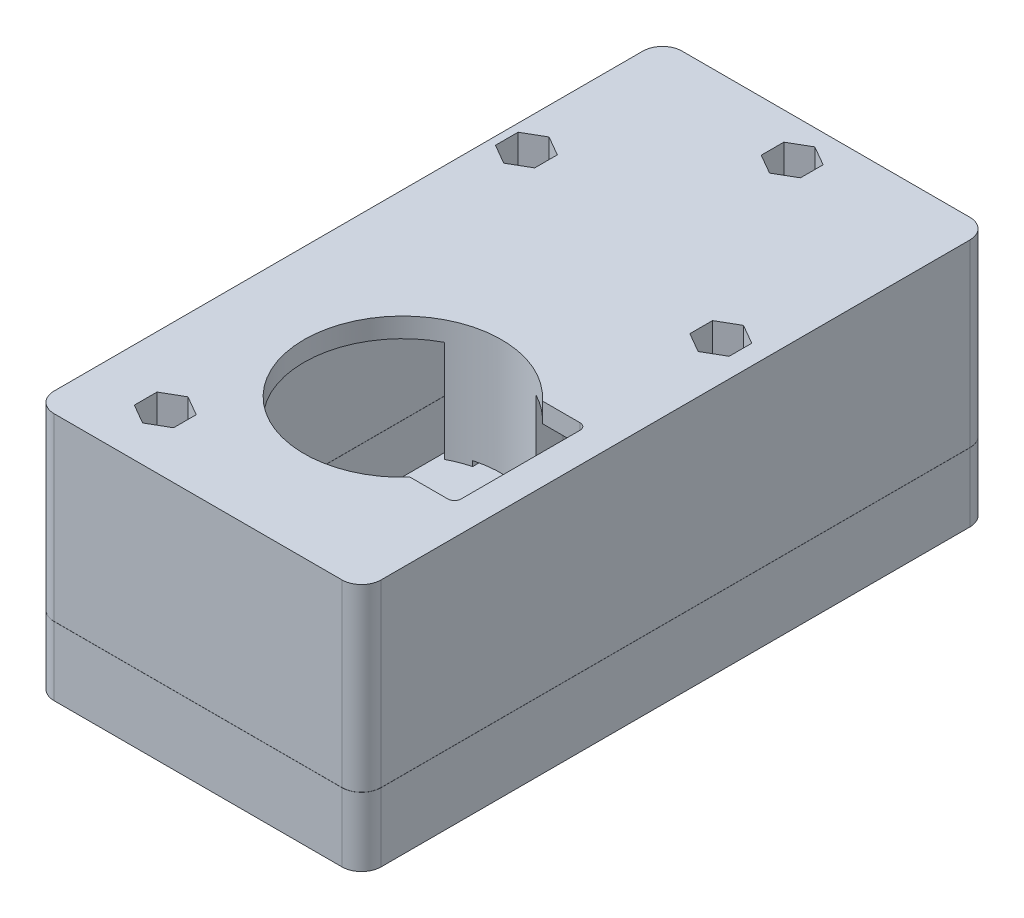
SolidWorks part; units mm, degrees
ref_plane "前视基准面" through (0, 0, 0) normal (0, 0, 1) x (1, 0, 0)
ref_plane "上视基准面" through (0, 0, 0) normal (0, 1, 0) x (1, 0, 0)
ref_plane "右视基准面" through (0, 0, 0) normal (1, 0, 0) x (0, 0, -1)
sketch "草图1" plane through (0, 0, 0) normal (0, 0, 1) x (1, 0, 0)
  line L1 (50, 38) -> (0, 38)
  line L2 (50, 38) -> (50, 0)
  line L3 (50, 0) -> (0, 0)
  line L4 (0, 38) -> (0, 0)
  dimension "D1" = 50
  dimension "D2" = 38
extrude "凸台-拉伸1" add sketch "草图1" against normal blind 3
sketch "草图2" plane through (0, 0, 0) normal (0, 0, 1) x (1, 0, 0)
  line L8 (50, 0) -> (50, 38)
  line L9 (50, 38) -> (0, 38)
  line L10 (0, 38) -> (0, 0)
  line L11 (0, 0) -> (50, 0)
  line L12 (50, 0) -> (50, 38)
  line L13 (50, 38) -> (0, 38)
  line L14 (0, 38) -> (0, 0)
  line L15 (0, 0) -> (50, 0)
  line L20 (47, 3) -> (47, 35)
  line L21 (47, 35) -> (3, 35)
  line L22 (3, 35) -> (3, 3)
  line L23 (3, 3) -> (47, 3)
  line L24 (47, 3) -> (47, 35)
  line L25 (47, 35) -> (3, 35)
  line L26 (3, 35) -> (3, 3)
  line L27 (3, 3) -> (47, 3)
  dimension "D1" = 0
  dimension "D2" = 3
extrude "凸台-拉伸2" add sketch "草图2" along normal blind 90
sketch "草图4" plane through (0, 0, -3) normal (0, 0, -1) x (-1, 0, 0)
  line L0 (-50, 38) -> (0, 38) construction
  line L1 (0, 38) -> (0, 0) construction
  circle A0 centre (-12.5, 10.5) radius 7.3
  dimension "D1" = 14.6
  dimension "D3" = 12.5
  dimension "D2" = 27.5
extrude "切除-拉伸1" cut sketch "草图4" against normal blind 45.2
sketch "草图5" plane through (0, 0, 0) normal (0, 0, 1) x (1, 0, 0)
  circle A0 centre (12.5, 10.5) radius 7.3
  circle A1 centre (12.5, 10.5) radius 7.3 construction
  circle A2 centre (12.5, 10.5) radius 10.3
  dimension "D1" = 3
extrude "凸台-拉伸3" add sketch "草图5" along normal blind 16
sketch "草图6" plane through (0, 0, -3) normal (0, 0, -1) x (-1, 0, 0)
  circle A0 centre (-12.5, 10.5) radius 5.8
  circle A3 centre (-12.5, 10.5) radius 7.3 construction
  circle A4 centre (-12.5, 10.5) radius 8.3
  circle A5 centre (-12.5, 10.5) radius 8.3
  dimension "D1" = 1
  dimension "D2" = 1.5
extrude "凸台-拉伸5" add sketch "草图6" against normal blind 1
sketch "草图7" plane through (0, 0, 16) normal (0, 0, 1) x (1, 0, 0)
  line L2 (5.4403, 3) -> (19.5597, 3)
  line L4 (5.4403, 3) -> (19.5597, 3)
  line L5 (3, 14.4799) -> (3, 6.5201)
  line L8 (3, 14.4799) -> (3, 6.5201)
  arc A1 (3, 6.5201) -> (5.4403, 3) centre (12.5, 10.5) ccw
  arc A2 (3, 6.5201) -> (5.4403, 3) centre (12.5, 10.5) ccw
  circle A3 centre (12.5, 10.5) radius 4.3
  arc A10 (19.5597, 3) -> (3, 14.4799) centre (12.5, 10.5) ccw
  arc A11 (19.5597, 3) -> (3, 14.4799) centre (12.5, 10.5) ccw
  dimension "D2" = 8.6
  dimension "D1" = 0
extrude "凸台-拉伸6" add sketch "草图7" along normal blind 2
sketch "草图8" plane through (0, 0, 18) normal (0, 0, 1) x (1, 0, 0)
  circle A1 centre (12.5, 10.5) radius 6.3
  circle A2 centre (12.5, 10.5) radius 4.3
  circle A3 centre (12.5, 10.5) radius 4.3
  dimension "D1" = 0
  dimension "D2" = 2
extrude "凸台-拉伸7" add sketch "草图8" along normal blind 10
sketch "草图9" plane through (0, 0, 28) normal (0, 0, 1) x (1, 0, 0)
  line L0 (8.2, 10.5) -> (16.8, 10.5) construction
  line L2 (16.1644, 8.25) -> (18.8, 8.25)
  line L3 (16.1644, 8.25) -> (16.1644, 12.75)
  line L4 (16.1644, 12.75) -> (18.8, 12.75)
  line L5 (18.8, 8.25) -> (18.8, 12.75)
  circle A0 centre (12.5, 10.5) radius 4.3 construction
  circle A1 centre (12.5, 10.5) radius 6.3 construction
  dimension "D1" = 4.5
extrude "切除-拉伸2" cut sketch "草图9" against normal blind 4
sketch "草图10" plane through (0, 3, 0) normal (0, 1, 0) x (1, 0, 0)
  line L0 (19.33, -36.76) -> (19.33, -34.76)
  line L1 (19.33, -34.76) -> (22.03, -34.76)
  line L2 (22.03, -34.76) -> (22.03, -36.76)
  line L3 (22.03, -36.76) -> (19.33, -36.76)
  line L8 (23.23, -37.46) -> (23.23, -28) construction
  line L9 (23.43, -37.46) -> (23.03, -37.46) construction
  line L10 (16.8, -28) -> (29.66, -28) construction
  line L11 (27.13, -34.76) -> (24.43, -34.76)
  line L12 (24.43, -34.76) -> (24.43, -36.76)
  line L13 (24.43, -36.76) -> (27.13, -36.76)
  line L14 (27.13, -36.76) -> (27.13, -34.76)
  line L15 (18.53, -37.26) -> (18.53, -34.14) construction
  line L16 (22.83, -37.26) -> (22.83, -34.14) construction
  line L17 (20.92, -34.36) -> (18.92, -34.36) construction
  circle A0 centre (19.92, -32.88) radius 0.7
  circle A1 centre (26.54, -32.88) radius 0.7
  circle A2 centre (19.92, -32.88) radius 0.98 construction
  point P14 (18.53, -35.7)
  dimension "D1" = 1.4
  dimension "D2" = 0.28
  dimension "D3" = 0.8
  dimension "D4" = 0.8
  dimension "D5" = 0.4
  dimension "D6" = 2
extrude "凸台-拉伸8" add sketch "草图10" along normal blind 32
sketch "草图11" plane through (0, 3, 0) normal (0, 1, 0) x (1, 0, 0)
  line L0 (16.8, -34.14) -> (16.8, -28) construction
  line L1 (16.2, -36.76) -> (30.26, -36.76)
  line L2 (16.2, -36.76) -> (16.2, -27.4)
  line L3 (16.2, -27.4) -> (30.26, -27.4)
  line L4 (30.26, -36.76) -> (30.26, -27.4)
  line L5 (29.66, -28) -> (29.66, -34.14) construction
  line L6 (19.33, -36.76) -> (22.03, -36.76) construction
  line L7 (16.8, -28) -> (29.66, -28) construction
  dimension "D1" = 0.6
  dimension "D2" = 0.6
  dimension "D3" = 0.6
extrude "凸台-拉伸9" add sketch "草图11" along normal blind 4.4
sketch "草图12" plane through (0, 35, 0) normal (0, -1, 0) x (1, 0, 0)
  line L1 (16.2, 27.4) -> (30.26, 27.4)
  line L2 (16.2, 27.4) -> (16.2, 36.76)
  line L3 (16.2, 36.76) -> (30.26, 36.76)
  line L4 (30.26, 27.4) -> (30.26, 36.76)
extrude "凸台-拉伸10" add sketch "草图12" along normal blind 21.2
sketch "草图13" plane through (0, 38, 0) normal (0, 1, 0) x (1, 0, 0)
  line L0 (12.3, -64.096) -> (42.5, -64.096) construction
  line L1 (40.04, -72.896) -> (39.0237, -72.896) construction
  line L2 (38.625, -74.196) -> (44.4, -74.196)
  line L3 (45.4, -73.196) -> (45.4, -54.996)
  line L4 (44.4, -57.796) -> (44.4, -70.396) construction
  line L5 (38.625, -53.996) -> (44.4, -53.996)
  circle A0 centre (27.4, -64.096) radius 15.1 construction
  circle A1 centre (27.4, -64.096) radius 14.1 construction
  arc A2 (38.625, -74.196) -> (38.625, -53.996) centre (27.4, -64.096) cw
  arc A3 (44.4, -53.996) -> (45.4, -54.996) centre (44.4, -54.996) cw
  arc A4 (44.4, -74.196) -> (45.4, -73.196) centre (44.4, -73.196) ccw
  point P16 (45.4, -64.096)
  point P18 (45.4, -53.996)
  point P21 (45.4, -74.196)
  dimension "D1" = 1
  dimension "D2" = 1.3
  dimension "D4" = 1
  dimension "D3" = 1
extrude "切除-拉伸3" cut sketch "草图13" against normal blind 3
sketch "草图14" plane through (0, 35, 0) normal (0, -1, 0) x (1, 0, 0)
  line L0 (14.3, 64.096) -> (40.5, 64.096) construction
  line L1 (23.9, 46.596) -> (23.9, 50.4373) construction
  line L2 (30.9, 46.596) -> (30.9, 50.4373) construction
  line L3 (23.9, 46.596) -> (23.9, 49.4072)
  line L4 (30.9, 46.596) -> (30.9, 49.4072)
  line L5 (30.9, 81.596) -> (30.9, 78.7847)
  line L6 (23.9, 81.596) -> (23.9, 78.7847)
  circle A0 centre (27.4, 46.596) radius 1.65
  circle A1 centre (27.4, 64.096) radius 13.1 construction
  arc A2 (23.9, 49.4072) -> (30.9, 49.4072) centre (27.4, 64.096) ccw
  arc A3 (38.625, 74.196) -> (38.625, 53.996) centre (27.4, 64.096) ccw construction
  arc A4 (23.9, 46.596) -> (30.9, 46.596) centre (27.4, 46.596) ccw
  arc A5 (23.9, 46.596) -> (30.9, 46.596) centre (27.4, 46.596) ccw construction
  arc A6 (23.9, 81.596) -> (30.9, 81.596) centre (27.4, 81.596) cw
  arc A7 (23.9, 78.7847) -> (30.9, 78.7847) centre (27.4, 64.096) cw
  circle A8 centre (27.4, 81.596) radius 1.65
  dimension "D1" = 3.3
extrude "凸台-拉伸11" add sketch "草图14" along normal blind 15.5
sketch "草图15" plane through (0, 35, 0) normal (0, -1, 0) x (1, 0, 0)
  line L0 (23.9, 46.596) -> (23.9, 50.4373) construction
  line L1 (20.4, 50.7165) -> (20.4, 46.596)
  line L2 (27.4, 48.696) -> (27.4, 44.496) construction
  line L4 (34.4, 50.7165) -> (34.4, 46.596)
  line L5 (45.4, 64.096) -> (12.3, 64.096) construction
  line L6 (45.4, 73.196) -> (45.4, 54.996) construction
  line L7 (20.4, 77.4754) -> (20.4, 81.596)
  line L8 (34.4, 77.4754) -> (34.4, 81.596)
  circle A0 centre (27.4, 46.596) radius 1.65
  circle A1 centre (27.4, 46.596) radius 2.1 construction
  arc A2 (20.4, 46.596) -> (34.4, 46.596) centre (27.4, 46.596) ccw
  arc A3 (20.4, 50.7165) -> (34.4, 50.7165) centre (27.4, 64.096) ccw
  arc A4 (23.9, 78.7847) -> (23.9, 49.4072) centre (27.4, 64.096) ccw construction
  arc A5 (20.4, 77.4754) -> (34.4, 77.4754) centre (27.4, 64.096) cw
  circle A6 centre (27.4, 81.596) radius 1.65
  arc A7 (20.4, 81.596) -> (34.4, 81.596) centre (27.4, 81.596) cw
  arc A9 (30.9, 49.4072) -> (38.625, 53.996) centre (27.4, 64.096) ccw construction
  line M14 (23.9, 78.7847) -> (23.9, 81.596)
  arc M15 (23.9, 81.596) -> (30.9, 81.596) centre (27.4, 81.596) cw
  line M16 (30.9, 81.596) -> (30.9, 78.7847)
  line M24 (30.9, 49.4072) -> (30.9, 46.596)
  arc M25 (30.9, 46.596) -> (23.9, 46.596) centre (27.4, 46.596) cw
  line M26 (23.9, 46.596) -> (23.9, 49.4072)
  dimension "D1" = 3.3
  dimension "D2" = 7
extrude "凸台-拉伸12" add sketch "草图15" along normal blind 15.5 contours L1 A2 L4 M24 M25 M26 | A7 L7 L8 M14 M15 M16 region at (22.0467, 35, 49.7857) region at (20.5788, 35, 79.5357)
sketch "草图16" plane through (0, 19.5, 0) normal (0, -1, 0) x (1, 0, 0)
  line L0 (45.4, 64.096) -> (12.3, 64.096) construction
  line L1 (45.4, 73.196) -> (45.4, 54.996) construction
  line L24 (31.3, 81.596) -> (31.3, 77.2291)
  line L25 (23.5, 77.2291) -> (23.5, 81.596)
  line L26 (31.3, 46.596) -> (31.3, 50.9628)
  line L27 (23.5, 50.9628) -> (23.5, 46.596)
  line L28 (31.3, 46.596) -> (31.3, 50.9628)
  line L29 (23.5, 50.9628) -> (23.5, 46.596)
  arc A0 (20.4, 77.4754) -> (20.4, 50.7165) centre (27.4, 64.096) ccw construction
  arc A25 (23.5, 81.596) -> (31.3, 81.596) centre (27.4, 81.596) cw
  arc A26 (23.5, 77.2291) -> (31.3, 77.2291) centre (27.4, 64.096) cw
  arc A27 (23.5, 50.9628) -> (31.3, 50.9628) centre (27.4, 64.096) ccw
  arc A28 (23.5, 46.596) -> (31.3, 46.596) centre (27.4, 46.596) ccw
  arc A29 (23.5, 50.9628) -> (31.3, 50.9628) centre (27.4, 64.096) ccw
  arc A30 (23.5, 46.596) -> (31.3, 46.596) centre (27.4, 46.596) ccw
  dimension "D1" = 0.4
extrude "切除-拉伸4" cut sketch "草图16" against normal blind 0.8
sketch "草图17" plane through (0, 0, 0) normal (0, 0, 1) x (1, 0, 0)
  line L1 (3, 3) -> (47, 3) construction
  line L2 (22.83, 10.5392) -> (22.83, 3)
  line L3 (22.83, 10.2892) -> (22.83, 10.7892) construction
  line L4 (22.83, 3) -> (19.5597, 3)
  line L5 (5.4403, 3) -> (3, 3)
  line L6 (3, 3) -> (3, 6.5201)
  line L7 (3, 14.4799) -> (3, 35)
  line L8 (3, 35) -> (22.83, 35)
  line L9 (47, 35) -> (3, 35) construction
  line L10 (22.83, 10.5392) -> (22.83, 35)
  arc A1 (5.4403, 3) -> (3, 6.5201) centre (12.5, 10.5) cw
  arc A2 (3, 6.5201) -> (5.4403, 3) centre (12.5, 10.5) ccw construction
  arc A3 (3, 14.4799) -> (19.5597, 3) centre (12.5, 10.5) cw
  arc M1 (3, 14.4799) -> (19.5597, 3) centre (12.5, 10.5) cw
  line M2 (19.5597, 3) -> (47, 3)
  line M4 (47, 35) -> (3, 35)
  line M5 (3, 35) -> (3, 14.4799)
extrude "凸台-拉伸13" add sketch "草图17" along normal blind 18 contours L2 L10 M4 M5 M1 M2 | L5 A1 L6 region at (13.2696, 26.2496, 0) region at (3.7547, 4.0789, 0)
sketch "草图18" plane through (0, 0, 18) normal (0, 0, 1) x (1, 0, 0)
  line L8 (3, 35) -> (3, 3)
  line L9 (3, 3) -> (22.83, 3)
  line L10 (22.83, 3) -> (22.83, 35)
  line L11 (22.83, 35) -> (3, 35)
  line L12 (3, 35) -> (3, 3)
  line L13 (3, 3) -> (22.83, 3)
  line L14 (22.83, 3) -> (22.83, 35)
  line L15 (22.83, 35) -> (3, 35)
  circle A0 centre (12.5, 10.5) radius 6.3
  circle A1 centre (12.5, 10.5) radius 6.3 construction
  dimension "D1" = 0
extrude "凸台-拉伸14" add sketch "草图18" along normal blind 10
sketch "草图19" plane through (0, 0, 28) normal (0, 0, 1) x (1, 0, 0)
  line L0 (18.3845, 8.25) -> (22.83, 8.25)
  line L1 (22.83, 7.4) -> (22.83, 13.8) construction
  line L2 (22.83, 8.25) -> (22.83, 12.75)
  line L3 (22.83, 12.75) -> (18.3845, 12.75)
  line L4 (18.3845, 12.75) -> (16.1644, 12.75) construction
  line L5 (18.3845, 8.25) -> (18.3845, 12.75)
extrude "切除-拉伸5" cut sketch "草图19" against normal blind 4
sketch "草图23" plane through (0, 35, 0) normal (0, -1, 0) x (1, 0, 0)
  line L0 (22.83, 27.4) -> (22.83, 0) construction
  line L1 (22.83, 0) -> (47, 0) construction
  line L2 (22.83, 0) -> (22.83, 9)
  line L3 (22.83, 0) -> (31.83, 0)
  line L4 (47, 90) -> (47, 0) construction
  line L5 (44, 26.08) -> (47, 26.08)
  line L6 (47, 26.08) -> (47, 38.08)
  line L7 (45.65, 32.08) -> (42.35, 32.08) construction
  line L8 (44, 38.08) -> (47, 38.08)
  line L9 (30.26, 32.08) -> (42.35, 32.08) construction
  line L10 (30.26, 36.76) -> (30.26, 27.4) construction
  line L11 (3, 90) -> (3, 28) construction
  line L12 (0, 90) -> (50, 90) construction
  line L13 (11, 82.35) -> (11, 85.65) construction
  line L14 (5, 90) -> (5, 84)
  line L15 (17, 90) -> (17, 84)
  line L16 (5, 90) -> (17, 90)
  circle A0 centre (25.83, 3) radius 1.65
  arc A1 (31.83, 0) -> (22.83, 9) centre (22.83, 0) ccw
  circle A2 centre (44, 32.08) radius 1.65
  arc A3 (44, 26.08) -> (44, 38.08) centre (44, 32.08) cw
  circle A4 centre (11, 84) radius 1.65
  arc A5 (5, 84) -> (17, 84) centre (11, 84) ccw
  point P22 (47, 32.08)
  dimension "D1" = 3
  dimension "D4" = 3.3
  dimension "D5" = 3
  dimension "D6" = 3.3
  dimension "D7" = 6
  dimension "D8" = 3.3
  dimension "D9" = 8
  dimension "D10" = 6
  dimension "D11" = 6
  dimension "D2" = 3
  dimension "D3" = 9
extrude "凸台-拉伸16" add sketch "草图23" along normal through all
sketch "草图25" plane through (0, 35, 0) normal (0, -1, 0) x (1, 0, 0)
  line L0 (0, -3) -> (0, 90) construction
  line L1 (16.2, 28) -> (3, 28) construction
  circle A0 centre (4.2, 22) radius 1.65
  circle A1 centre (4.2, 22) radius 3 construction
  circle A2 centre (25.83, 3) radius 1.65
  circle A7 centre (44, 32.08) radius 1.65
  circle A8 centre (44, 32.08) radius 1.65
  circle A10 centre (11, 84) radius 1.65
  circle A11 centre (11, 84) radius 1.65
  dimension "D1" = 3.3
  dimension "D2" = 6
  dimension "D3" = 4.2
  dimension "D4" = 6
  dimension "D5" = 0
  dimension "D6" = 0
extrude "切除-拉伸7" cut sketch "草图25" against normal through all and the other way through all
sketch "草图26" plane through (0, 38, 0) normal (0, 1, 0) x (1, 0, 0)
  line L0 (0, 3) -> (0, -90) construction
  line L1 (4.2, -18.5371) -> (1.201, -20.2685)
  line L2 (1.201, -20.2685) -> (1.201, -23.7315)
  line L3 (1.201, -23.7315) -> (4.2, -25.4629)
  line L4 (4.2, -25.4629) -> (7.199, -23.7315)
  line L5 (7.199, -23.7315) -> (7.199, -20.2685)
  line L6 (7.199, -20.2685) -> (4.2, -18.5371)
  line L7 (25.83, -6.4629) -> (28.829, -4.7315)
  line L8 (28.829, -4.7315) -> (28.829, -1.2685)
  line L9 (28.829, -1.2685) -> (25.83, 0.4629)
  line L10 (25.83, 0.4629) -> (22.831, -1.2685)
  line L11 (22.831, -1.2685) -> (22.831, -4.7315)
  line L12 (22.831, -4.7315) -> (25.83, -6.4629)
  line L14 (11, -80.5371) -> (8.001, -82.2685)
  line L15 (8.001, -82.2685) -> (8.001, -85.7315)
  line L16 (8.001, -85.7315) -> (11, -87.4629)
  line L17 (11, -87.4629) -> (13.999, -85.7315)
  line L18 (13.999, -85.7315) -> (13.999, -82.2685)
  line L19 (13.999, -82.2685) -> (11, -80.5371)
  line L20 (44, -28.6171) -> (41.001, -30.3485)
  line L21 (41.001, -30.3485) -> (41.001, -33.8115)
  line L22 (41.001, -33.8115) -> (44, -35.5429)
  line L23 (44, -35.5429) -> (46.999, -33.8115)
  line L24 (46.999, -33.8115) -> (46.999, -30.3485)
  line L25 (46.999, -30.3485) -> (44, -28.6171)
  circle A0 centre (4.2, -22) radius 2.999 construction
  circle A1 centre (25.83, -3) radius 2.999 construction
  circle A2 centre (11, -84) radius 2.999 construction
  circle A3 centre (44, -32.08) radius 2.999 construction
  dimension "D1" = 5.998
extrude "切除-拉伸8" cut sketch "草图26" against normal blind 24.5
sketch "草图29" plane through (0, 0, 90) normal (0, 0, 1) x (1, 0, 0)
  line L8 (0, 0) -> (50, 0)
  line L9 (50, 0) -> (50, 38)
  line L10 (50, 38) -> (0, 38)
  line L11 (0, 38) -> (0, 0)
  line L12 (0, 0) -> (50, 0)
  line L13 (50, 0) -> (50, 38)
  line L14 (50, 38) -> (0, 38)
  line L15 (0, 38) -> (0, 0)
  dimension "D1" = 0
extrude "凸台-拉伸17" add sketch "草图29" along normal blind 3
fillet "圆角1" radius 3 4 edges at (50, 19, 93) (50, 19, -3) (0, 19, 93) (0, 19, -3)
ref_plane "基准面3" through (0, 10.5, 0) normal (0, 1, 0) x (1, 0, 0)
sketch "草图30" plane through (50, 0, 0) normal (1, 0, 0) x (0, 0, -1)
  line L0 (-93, 0) -> (-93, 38) construction
  line L1 (-93, 10.51) -> (3, 10.51)
  line L2 (-93, 10.51) -> (-93, 10.49)
  line L3 (-93, 10.49) -> (3, 10.49)
  line L4 (3, 10.51) -> (3, 10.49)
  line L5 (3, 38) -> (3, 0) construction
  line L6 (27.5, 10.5) -> (-27.5, 10.5) construction
  dimension "D1" = 0.01
  dimension "D2" = 0.01
extrude "切除-拉伸9" cut sketch "草图30" against normal through all
